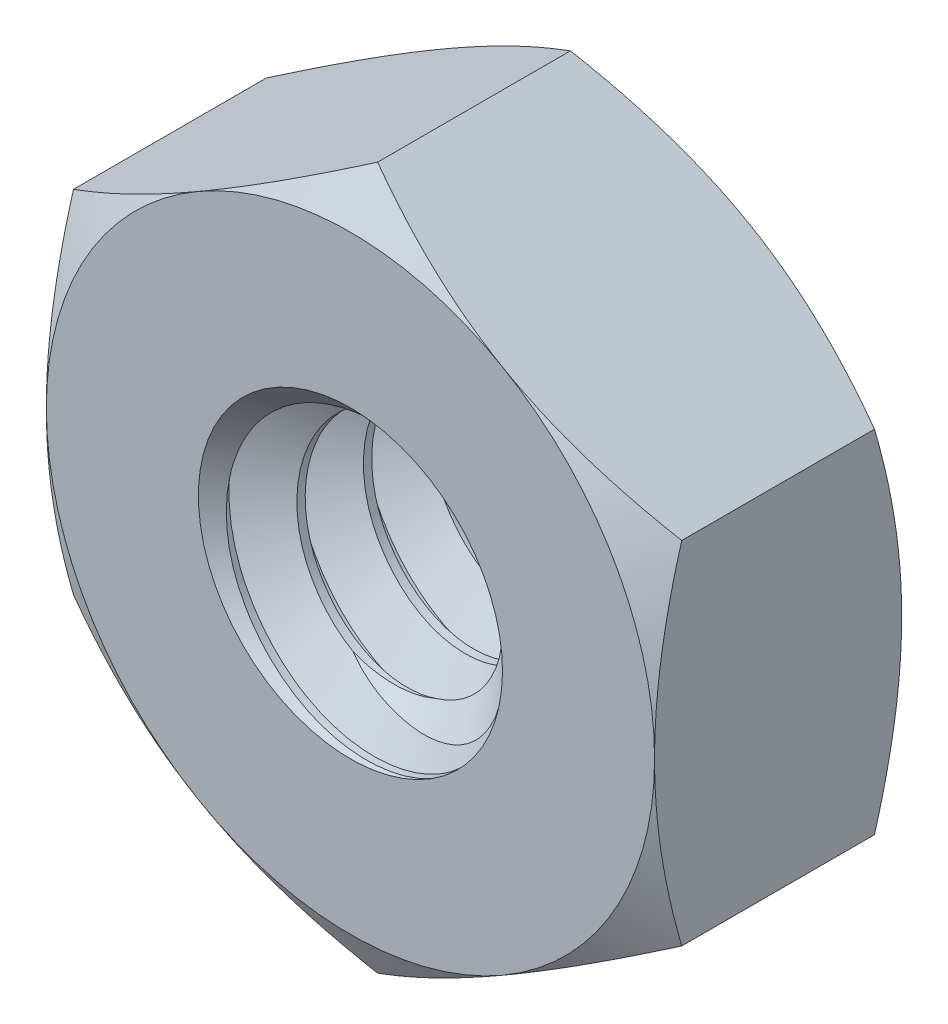
SolidWorks part; units mm, degrees
ref_plane "Front" through (0, 0, 0) normal (0, 0, 1) x (1, 0, 0)
ref_plane "Top" through (0, 0, 0) normal (0, 1, 0) x (1, 0, 0)
ref_plane "Right" through (0, 0, 0) normal (1, 0, 0) x (0, 0, -1)
sketch "Sketch1" plane through (0, 0, 0) normal (0, 0, 1) x (1, 0, 0)
  line L1 (-1.6, 0.9238) -> (-1.6, -0.9238)
  line L2 (-1.6, -0.9238) -> (0, -1.8475)
  line L3 (0, -1.8475) -> (1.6, -0.9238)
  line L4 (1.6, -0.9238) -> (1.6, 0.9238)
  line L5 (1.6, 0.9238) -> (0, 1.8475)
  line L6 (0, 1.8475) -> (-1.6, 0.9238)
  circle A0 centre (0, 0) radius 1.6 construction
  circle A1 centre (0, 0) radius 0.8 construction
  point P10 (0, 0.8)
  dimension "hex" = 3.2
  dimension "dia" = 1.6
extrude "Extrude1" add sketch "Sketch1" along normal mid plane 1.3
sketch "Sketch4" plane through (0, 0, -0.65) normal (0, 0, -1) x (-1, 0, 0)
  circle A0 centre (0, 0) radius 0.8 construction
  circle A1 centre (0, 0) radius 0.8
sketch "Sketch10" plane through (0, 0, 0.65) normal (0, 0, 1) x (1, 0, 0)
  circle A0 centre (0, 0) radius 0.8 construction
  circle A1 centre (0, 0) radius 0.8
extrude "Cut-Extrude2" cut sketch "Sketch10" against normal through all draft 45
sketch "Sketch11" plane through (0, 0, -0.65) normal (0, 0, -1) x (-1, 0, 0)
  circle A0 centre (0, 0) radius 0.8 construction
  circle A1 centre (0, 0) radius 0.8
extrude "Cut-Extrude3" cut sketch "Sketch11" against normal through all draft 45
sketch "Sketch13" plane through (0, 0, -0.65) normal (0, 0, -1) x (-1, 0, 0)
  circle A0 centre (0, 0) radius 0.8 construction
  circle A1 centre (0, 0) radius 0.8
extrude "Boss-Extrude1" add sketch "Sketch13" against normal up to vertex (1.3 mm away) separate body up to point (-1.6, 0.9238, 0.65)
curve "Helix/Spiral3" pitch 0.35 height 1.3 radius 0.8 centre (0, 0, -0.65) axis (0, 0, 1) start towards (0, 1, 0)
sketch "Sketch12" plane through (0, 0, 0) normal (1, 0, 0) x (0, 0, -1)
  line L0 (0.9563, 0.8) -> (0.65, 0.8)
  line L1 (0.9563, 0.8) -> (0.825, 0.5727)
  line L2 (0.825, 0.5727) -> (0.7812, 0.5727)
  line L3 (0.7812, 0.5727) -> (0.65, 0.8)
  line L4 (0.8031, 0.5727) -> (0.8031, 0.8) construction
  line L5 (0.7156, 0.6863) -> (0.8906, 0.6863) construction
  dimension "D1" = 60
  dimension "D2" = 0.0437
  dimension "D3" = 0.175
sweep "Cut-Sweep1" cut profiles "Sketch12" path "Helix/Spiral3" align with end faces yes
combine bodies "Combine1" operation type subtract main body 116 bodies to subtract 118
sketch "Sketch7" plane through (0, 0, 0.65) normal (0, 0, 1) x (1, 0, 0)
  circle A0 centre (0, 0) radius 1.6 construction
  circle A1 centre (0, 0) radius 1.6
extrude "Extrude2" cut sketch "Sketch7" against normal blind 25.4 draft 60 flip side to cut
mirror "Mirror2" about plane through (0, 0, 0) normal (0, 0, 1) of "Extrude2"
sketch "Sketch8" plane through (0, 0, 0.65) normal (0, 0, 1) x (1, 0, 0)
  line L0 (-0.5657, 0.5657) -> (0, 0) construction
  line L1 (0, -0.6275) -> (0, 0.6275) construction
  circle A1 centre (0, 0) radius 0.8 construction
  point P0 (-0.5657, 0.5657)
  dimension "D1" = 45
sketch "Sketch14" plane through (0, 0, 0.65) normal (0, 0, 1) x (1, 0, 0)
  line L0 (0, 0) -> (-0.8, 0) construction
  arc A0 (0.4245, -0.6781) -> (0.7814, -0.1714) centre (0, 0) ccw construction
equation "\"D3@Helix/Spiral3\" = \"length@Extrude1\" "
equation "\"D2@Sketch12\" = \"D4@Helix/Spiral3\"*.125"
equation "\"D3@Sketch12\" = \"D4@Helix/Spiral3\"*.50"
